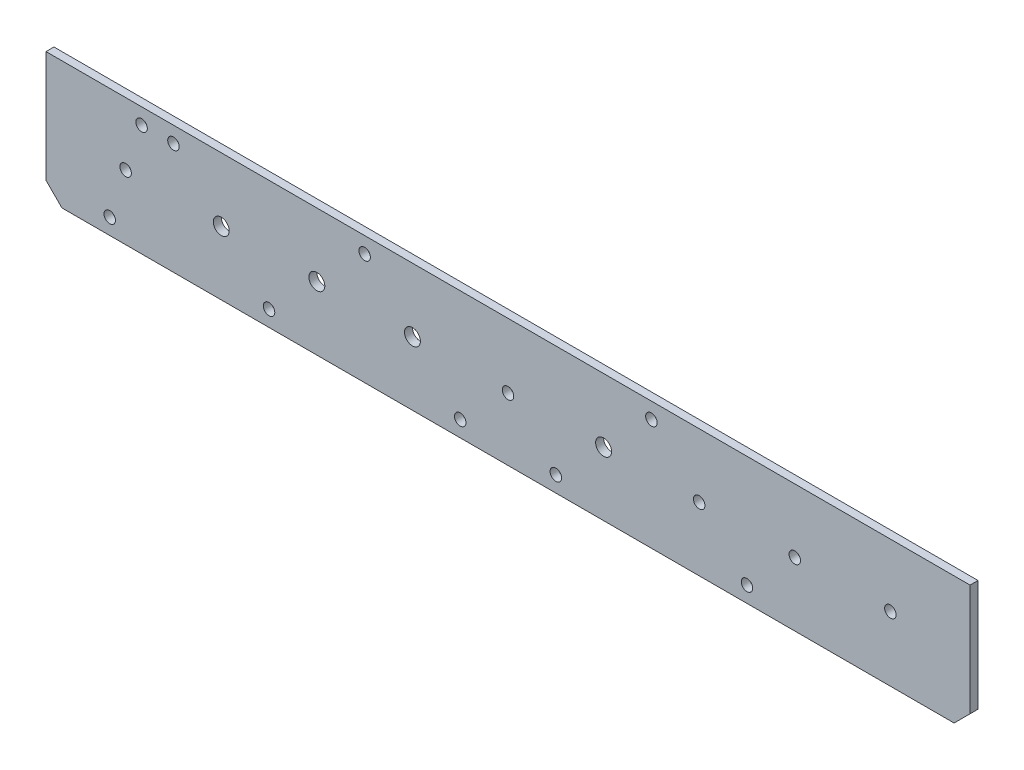
SolidWorks part; units mm, degrees
ref_plane "Front Plane" through (0, 0, 0) normal (0, 0, 1) x (1, 0, 0)
ref_plane "Top Plane" through (0, 0, 0) normal (0, 1, 0) x (1, 0, 0)
ref_plane "Right Plane" through (0, 0, 0) normal (1, 0, 0) x (0, 0, -1)
sketch "Sketch1" plane through (0, 0, 0) normal (0, 0, 1) x (1, 0, 0)
  line L1 (0, 0) -> (368.3, 0)
  line L2 (0, 0) -> (0, 50.8)
  line L3 (0, 50.8) -> (368.3, 50.8)
  line L4 (368.3, 0) -> (368.3, 50.8)
  dimension "D1" = 50.8
  dimension "D2" = 368.3
extrude "Boss-Extrude1" add sketch "Sketch1" along normal blind 3.175
sketch "Sketch2" plane through (0, 0, 3.175) normal (0, 0, 1) x (1, 0, 0)
  line L0 (184.15, 25.0031) -> (31.75, 25.7969) construction
  line L1 (184.15, 50.8) -> (184.15, 0) construction
  line L2 (368.3, 50.8) -> (0, 50.8) construction
  line L3 (0, 0) -> (368.3, 0) construction
  line L4 (184.15, 25.0031) -> (336.55, 25.7969) construction
  line L5 (0, 6.35) -> (0, 0)
  line L6 (0, 50.8) -> (0, 0) construction
  line L7 (0, 0) -> (6.35, 0)
  line L8 (6.35, 0) -> (0, 6.35)
  line L9 (368.3, 0) -> (361.95, 0)
  line L10 (361.95, 0) -> (368.3, 6.35)
  line L11 (368.3, 6.35) -> (368.3, 0)
  circle A0 centre (31.75, 25.7969) radius 2.286
  circle A1 centre (184.15, 25.0031) radius 2.286
  circle A2 centre (107.95, 25.4) radius 3.175
  circle A3 centre (69.85, 25.4) radius 3.175
  circle A4 centre (146.05, 25.4) radius 3.175
  circle A5 centre (222.25, 25.4) radius 3.175
  circle A6 centre (298.45, 25.4) radius 2.286
  circle A7 centre (260.35, 25.4) radius 2.286
  circle A8 centre (336.55, 25.7969) radius 2.286
  circle A9 centre (50.8, 44.45) radius 2.286
  circle A10 centre (165.1, 6.35) radius 2.286
  circle A11 centre (203.2, 6.35) radius 2.286
  circle A13 centre (127, 44.45) radius 2.286
  circle A14 centre (241.3, 44.45) radius 2.286
  circle A15 centre (88.9, 6.35) radius 2.286
  circle A16 centre (279.4, 6.35) radius 2.286
  circle A17 centre (38.1, 44.45) radius 2.286
  circle A18 centre (25.4, 6.35) radius 2.286
  point P17 (184.15, 25.4)
  point P52 (0, 0)
  point P53 (0, 0)
  dimension "D2" = 4.572
  dimension "D5" = 6.35
  dimension "D7" = 4.572
  dimension "D12" = 4.572
  dimension "D15" = 4.572
  dimension "D16" = 4.572
  dimension "D19" = 4.572
  dimension "D21" = 6.35
  dimension "D1" = 0.7937
  dimension "D3" = 38.1
  dimension "D4" = 152.4
  dimension "D6" = 38.1
  dimension "D8" = 57.15
  dimension "D9" = 19.05
  dimension "D10" = 57.15
  dimension "D11" = 19.05
  dimension "D13" = 57.15
  dimension "D14" = 19.05
  dimension "D17" = 19.05
  dimension "D18" = 19.05
  dimension "D20" = 19.05
  dimension "D22" = 6.35
  dimension "D23" = 6.35
  dimension "D24" = 6.35
extrude "Cut-Extrude1" cut sketch "Sketch2" against normal up to next
